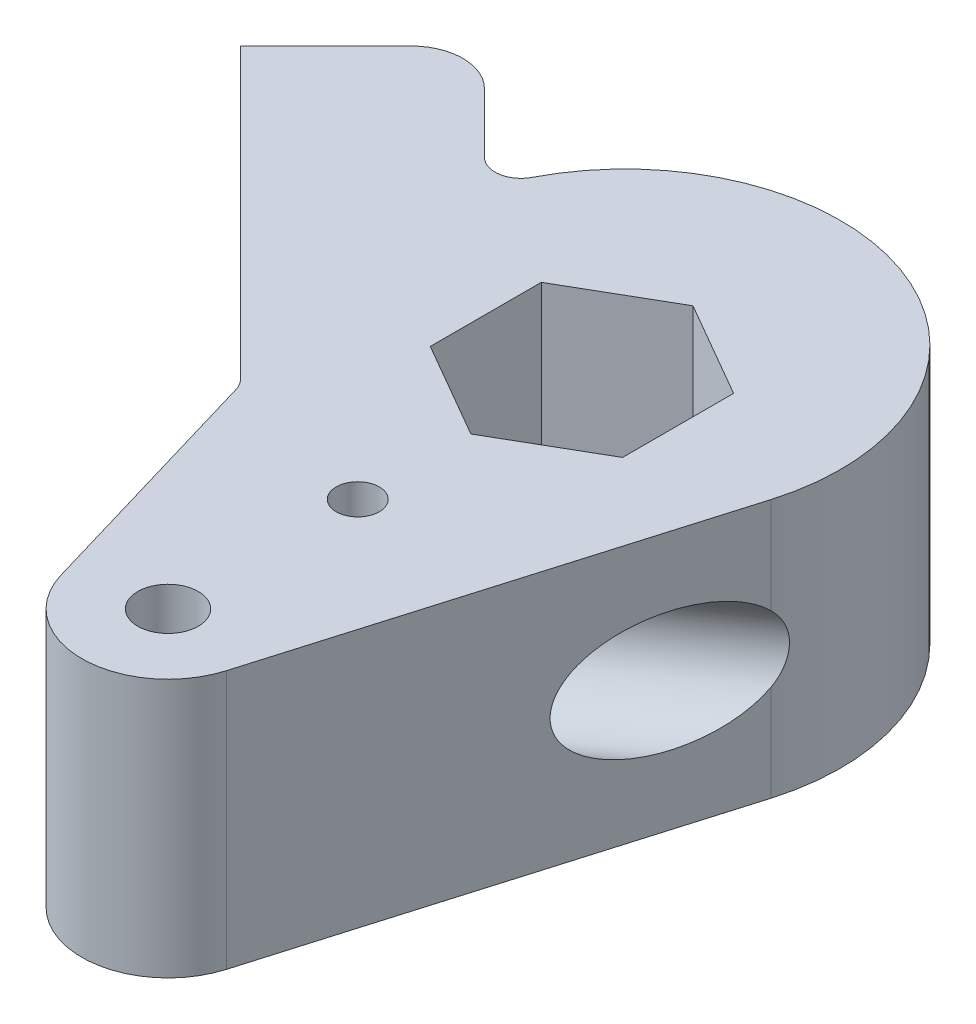
SolidWorks part; units mm, degrees
ref_plane "Front Plane" through (0, 0, 0) normal (0, 0, 1) x (1, 0, 0)
ref_plane "Top Plane" through (0, 0, 0) normal (0, 1, 0) x (1, 0, 0)
ref_plane "Right Plane" through (0, 0, 0) normal (1, 0, 0) x (0, 0, -1)
ref_axis "Axis1" through (0, 14.8656, 0) along (0, -1, 0)
sketch "Sketch1" plane through (0, 0, 0) normal (0, 1, 0) x (1, 0, 0)
  line L0 (0, 15) -> (0, -15) construction
  line L5 (-12.5, 15) -> (12.5, 15) construction
  line L7 (-12.5, 15) -> (-12.5, -15) construction
  line L10 (-12.5, -15) -> (12.5, -15) construction
  line L11 (12.5, 15) -> (12.5, -15) construction
  line L12 (-4.7956, -25.4151) -> (-11.9889, -1.0377)
  line L13 (0, -6.4375) -> (5.575, -3.2187)
  line L14 (5.575, -3.2187) -> (5.575, 3.2187)
  line L15 (5.575, 3.2187) -> (0, 6.4375)
  line L16 (0, 6.4375) -> (-5.575, 3.2187)
  line L17 (-5.575, 3.2187) -> (-5.575, -3.2187)
  line L18 (-5.575, -3.2187) -> (0, -6.4375)
  line L21 (11.9889, -1.0377) -> (4.7956, -25.4151)
  circle A0 centre (0, 0) radius 5.575 construction
  circle A1 centre (0, -24) radius 1.75
  arc A2 (-4.7956, -25.4151) -> (4.7956, -25.4151) centre (0, -24) ccw
  arc A4 (-11.9889, -1.0377) -> (11.9889, -1.0377) centre (0, 2.5) cw
  dimension "D3" = 15
  dimension "D4" = 11.15
  dimension "D5" = 24
  dimension "D1" = 25
  dimension "D6" = 3.5
  dimension "D7" = 5
  dimension "D2" = 30
extrude "Boss-Extrude1" add sketch "Sketch1" along normal blind 15
sketch "Sketch10" plane through (0, 0, 0) normal (0, 1, 0) x (1, 0, 0)
  circle A0 centre (0, -13) radius 1.25
  dimension "D2" = 2.5
  dimension "D1" = 13
extrude "Cut-Extrude3" cut sketch "Sketch10" along normal through all
ref_axis "Axis2" through (0, 15, 13) along (0, -1, 0)
ref_plane "Plane1" through (-6.108, 0, 4.2769) normal (0.8192, 0, -0.5736) x (0, -1, 0)
sketch "Sketch11" plane through (7.806, 0, 24.1481) normal (-0.8192, 0, 0.5736) x (0.5736, 0, 0.8192)
  line L1 (-12.3594, 15) -> (-14.8594, 15) construction
  line L3 (-12.3594, 15) -> (-14.8594, 15) construction
  line L4 (-13.6094, 15) -> (-13.6094, 0) construction
  line L5 (-14.8594, 0) -> (-12.3594, 0) construction
  line L6 (-14.8594, 0) -> (-12.3594, 0) construction
  circle A0 centre (-13.6094, 7.5) radius 1.95
  dimension "D1" = 3.9
extrude "Cut-Extrude4" cut sketch "Sketch11" against normal through all
sketch "Sketch12" plane through (0, 0, 0) normal (0, 1, 0) x (1, 0, 0)
  line L12 (5.575, -3.2187) -> (5.575, 3.2187) construction
  line L13 (0, -6.4375) -> (5.575, -3.2187) construction
  line L14 (-5.575, -3.2187) -> (0, -6.4375) construction
  line L15 (-5.575, 3.2187) -> (-5.575, -3.2187) construction
  line L16 (0, 6.4375) -> (-5.575, 3.2187) construction
  line L17 (5.575, 3.2187) -> (0, 6.4375) construction
  line L18 (5.575, -3.2187) -> (5.575, 3.2187)
  line L19 (0, -6.4375) -> (5.575, -3.2187)
  line L20 (-5.575, -3.2187) -> (0, -6.4375)
  line L21 (-5.575, 3.2187) -> (-5.575, -3.2187)
  line L22 (0, 6.4375) -> (-5.575, 3.2187)
  line L23 (5.575, 3.2187) -> (0, 6.4375)
  circle A0 centre (0, 0) radius 3.5
  dimension "D1" = 7
extrude "Boss-Extrude8" add sketch "Sketch12" along normal blind 5
sketch "Sketch13" plane through (0, 0, 0) normal (0, 1, 0) x (1, 0, 0)
  line L0 (0, 0) -> (0, -24) construction
  line L1 (-19.0919, 13.435) -> (-26.163, 6.364)
  line L2 (-19.0919, 13.435) -> (-0.9289, -4.7279) construction
  line L3 (-26.163, 6.364) -> (-8, -11.799)
  line L4 (-0.9289, -4.7279) -> (-8, -11.799) construction
  line L5 (-19.0919, 13.435) -> (-8, -11.799) construction
  line L6 (-26.163, 6.364) -> (-0.9289, -4.7279) construction
  line L7 (-19.0919, 13.435) -> (-8, 2.3431)
  line L8 (-8, 2.3431) -> (-8, -11.799)
  point P5 (-13.5459, 0.818)
  dimension "D1" = 10
  dimension "D2" = 23
  dimension "D3" = 45
  dimension "D4" = 14
  dimension "D5" = 8
extrude "Boss-Extrude9" add sketch "Sketch13" along normal up to surface (15 mm away) up to face at (0, 15, 14.25)
sketch "Sketch14" plane through (-9.8995, 0, 9.8995) normal (-0.7071, 0, 0.7071) x (0.7071, 0, 0.7071)
  line L0 (-18, 15) -> (-18, 0) construction
  line L1 (-23, 15) -> (1.0543, 15) construction
  line L2 (-23, 0) -> (1.0543, 0) construction
  line L3 (-23, 15) -> (-23, 0) construction
  circle A0 centre (-18, 7.5) radius 2.75
  dimension "D1" = 5
  dimension "D2" = 5.5
extrude "Cut-Extrude5" cut sketch "Sketch14" against normal through all
fillet "Fillet1" radius 3 1 edges at (-19.0919, 7.5, -13.435)
fillet "Fillet2" radius 1.5 2 edges at (-9.154, 7.5, 10.645) (-11.9201, 7.5, -6.2632)
ref_plane "Plane2" through (10.275, 0, -7.1947) normal (0.8192, 0, -0.5736) x (0, -1, 0)
sketch "Sketch15" plane through (10.275, 0, -7.1947) normal (0.8192, 0, -0.5736) x (0, -1, 0)
  circle A0 centre (-7.5, -10.649) radius 1.95 construction
  circle A1 centre (-7.5, -10.649) radius 1.95 construction
  circle A2 centre (-7.5, -10.649) radius 3.5
  dimension "D1" = 7
extrude "Cut-Extrude6" cut sketch "Sketch15" against normal offset from surface (13 mm away) 7 up to plane "Plane1"
